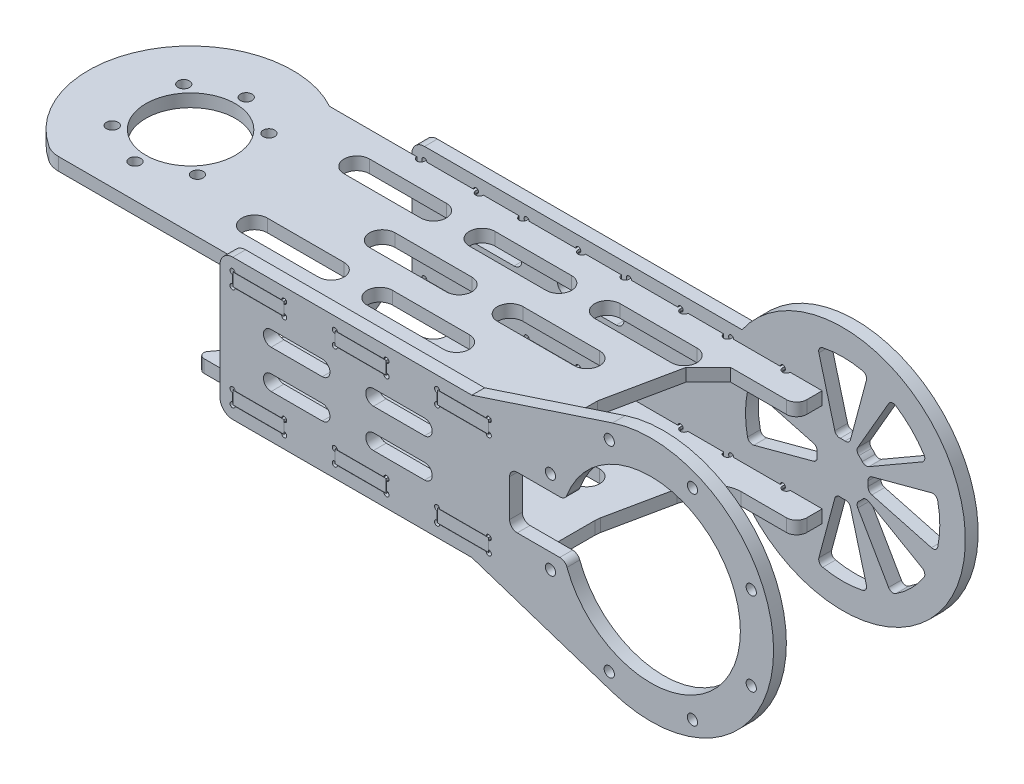
SolidWorks part; units mm, degrees
material "Thornel Mat VMA"
ref_plane "前视基准面" through (0, 0, 0) normal (0, 0, 1) x (1, 0, 0)
ref_plane "上视基准面" through (0, 0, 0) normal (0, 1, 0) x (1, 0, 0)
ref_plane "右视基准面" through (0, 0, 0) normal (1, 0, 0) x (0, 0, -1)
other "Configuration Table"
sketch "草图1" plane through (0, 0, 0) normal (0, 0, 1) x (1, 0, 0)
  line L0 (-270, 0) -> (0, 0)
  dimension "D1" = 270
extrude "拉伸-薄壁1" add sketch "草图1" along normal blind 200 thin
sketch "草图2" plane through (0, 0, 0) normal (0, 1, 0) x (1, 0, 0)
  line L0 (-270, -200) -> (0, -200) construction
  line L4 (-230, -165) -> (-230, -8.8813) construction
  line L5 (-230, -165) -> (-213.3385, -151.0194) construction
  line L6 (-270, -200) -> (-270, 0) construction
  line L7 (-247.5, -165) -> (-212.5, -165) construction
  line L8 (-270, -165) -> (-270, 0)
  line L9 (-270, 0) -> (0, 0) construction
  line L10 (-270, 0) -> (0, 0)
  line L11 (0, -200) -> (0, 0) construction
  line L12 (0, -130) -> (0, 0)
  line L13 (-210.6351, -130) -> (0, -130)
  line L14 (-270, -165) -> (-270, -200)
  line L15 (-270, -200) -> (-249.3649, -200)
  circle A0 centre (-230, -165) radius 21.75 construction
  circle A2 centre (-230, -143.25) radius 2.25
  circle A3 centre (-213.3385, -151.0194) radius 2.25
  circle A4 centre (-246.6615, -151.0194) radius 2.25
  circle A17 centre (-230, -165) radius 17.5
  circle A19 centre (-213.3385, -178.9806) radius 2.25
  circle A20 centre (-230, -186.75) radius 2.25
  circle A21 centre (-246.6615, -178.9806) radius 2.25
  arc A22 (-210.6351, -130) -> (-270, -165) centre (-230, -165) ccw
  arc A24 (-210.6351, -130) -> (-249.3649, -200) centre (-230, -165) ccw
  line M4 (0, 0) -> (-270, 0)
  line M5 (-270, 0) -> (-270, -200)
  line M6 (-270, -200) -> (0, -200)
  line M7 (0, -200) -> (0, 0)
  dimension "D1" = 35
  dimension "D2" = 43.5
  dimension "D4" = 4.5
  dimension "D6" = 80
  dimension "D7" = 35
  dimension "D9" = 35
  dimension "D3" = 40
  dimension "D5" = 50
extrude "切除-拉伸1" cut sketch "草图2" against normal blind 10 contours A22 L13 M7 M4 M5 | A24 M5 M6 | A21 | A17 | A4 | A2 | A3 | A19 | A20
fillet "圆角4" radius 10 1 edges at (-249.3649, -2.5, 200)
sketch "草图5" plane through (0, -5, 0) normal (0, -1, 0) x (1, 0, 0)
  line L0 (-246.5831, 200) -> (0, 200) construction
  line L2 (-180, 200) -> (-20, 200)
  line L3 (-180, 200) -> (-180, 206)
  line L4 (-180, 206) -> (-20, 206)
  line L5 (-20, 200) -> (-20, 206)
  line L6 (0, 200) -> (0, 130) construction
  line L7 (-210.6351, 130) -> (0, 130) construction
  line L8 (-180, 130) -> (-20, 130)
  line L9 (-180, 130) -> (-180, 124)
  line L10 (-180, 124) -> (-20, 124)
  line L11 (-20, 130) -> (-20, 124)
  circle A0 centre (-230, 165) radius 17.5 construction
  dimension "D1" = 6
  dimension "D2" = 50
  dimension "D3" = 20
  dimension "D4" = 6
  dimension "D5" = 20
  dimension "D6" = 50
extrude "凸台-拉伸1" add sketch "草图5" against normal blind 5
sketch "草图6" plane through (0, -5, 0) normal (0, -1, 0) x (1, 0, 0)
  line L0 (-180, 200) -> (-176.5, 200)
  line L1 (-173.5, 200) -> (-173.5, 205)
  line L2 (-173.5, 205) -> (-153.5, 205)
  line L3 (-153.5, 205) -> (-153.5, 200)
  line L4 (-150.5, 200) -> (-136.5, 200)
  line L5 (-180, 206) -> (-180, 200) construction
  line L6 (-20, 206) -> (-180, 206) construction
  line L7 (-20, 206) -> (-180, 206)
  line L8 (-180, 206) -> (-180, 200)
  line L9 (-133.5, 200) -> (-133.5, 205)
  line L10 (-133.5, 205) -> (-113.5, 205)
  line L11 (-113.5, 205) -> (-113.5, 200)
  line L12 (-110.5, 200) -> (-96.5, 200)
  line L13 (-93.5, 200) -> (-93.5, 205)
  line L14 (-93.5, 205) -> (-73.5, 205)
  line L15 (-73.5, 205) -> (-73.5, 200)
  line L16 (-70.5, 200) -> (-56.5, 200)
  line L17 (-53.5, 200) -> (-53.5, 205)
  line L18 (-53.5, 205) -> (-33.5, 205)
  line L19 (-33.5, 205) -> (-33.5, 200)
  line L20 (-30.5, 200) -> (-20, 200)
  line L21 (-20, 206) -> (-20, 200)
  line L22 (-212.5, 165) -> (-121.566, 165) construction
  line L23 (-20, 124) -> (-20, 130)
  line L24 (-30.5, 130) -> (-20, 130)
  line L25 (-33.5, 125) -> (-33.5, 130)
  line L26 (-53.5, 125) -> (-33.5, 125)
  line L27 (-53.5, 130) -> (-53.5, 125)
  line L28 (-70.5, 130) -> (-56.5, 130)
  line L29 (-73.5, 125) -> (-73.5, 130)
  line L30 (-93.5, 125) -> (-73.5, 125)
  line L31 (-93.5, 130) -> (-93.5, 125)
  line L32 (-110.5, 130) -> (-96.5, 130)
  line L33 (-113.5, 125) -> (-113.5, 130)
  line L34 (-133.5, 125) -> (-113.5, 125)
  line L35 (-133.5, 130) -> (-133.5, 125)
  line L36 (-180, 124) -> (-180, 130)
  line L37 (-20, 124) -> (-180, 124)
  line L38 (-150.5, 130) -> (-136.5, 130)
  line L39 (-153.5, 125) -> (-153.5, 130)
  line L40 (-173.5, 125) -> (-153.5, 125)
  line L41 (-173.5, 130) -> (-173.5, 125)
  line L42 (-180, 130) -> (-176.5, 130)
  arc A1 (-176.5, 200) -> (-173.5, 200) centre (-175, 200) ccw
  arc A2 (-153.5, 200) -> (-150.5, 200) centre (-152, 200) ccw
  arc A3 (-136.5, 200) -> (-133.5, 200) centre (-135, 200) ccw
  arc A4 (-113.5, 200) -> (-110.5, 200) centre (-112, 200) ccw
  arc A5 (-96.5, 200) -> (-93.5, 200) centre (-95, 200) ccw
  arc A6 (-73.5, 200) -> (-70.5, 200) centre (-72, 200) ccw
  arc A7 (-56.5, 200) -> (-53.5, 200) centre (-55, 200) ccw
  arc A8 (-33.5, 200) -> (-30.5, 200) centre (-32, 200) ccw
  circle A9 centre (-230, 165) radius 17.5 construction
  arc A10 (-33.5, 130) -> (-30.5, 130) centre (-32, 130) cw
  arc A11 (-56.5, 130) -> (-53.5, 130) centre (-55, 130) cw
  arc A12 (-73.5, 130) -> (-70.5, 130) centre (-72, 130) cw
  arc A13 (-96.5, 130) -> (-93.5, 130) centre (-95, 130) cw
  arc A14 (-113.5, 130) -> (-110.5, 130) centre (-112, 130) cw
  arc A15 (-136.5, 130) -> (-133.5, 130) centre (-135, 130) cw
  arc A16 (-153.5, 130) -> (-150.5, 130) centre (-152, 130) cw
  arc A17 (-176.5, 130) -> (-173.5, 130) centre (-175, 130) cw
  dimension "D1" = 3
  dimension "D2" = 5
  dimension "D5" = 3
  dimension "D8" = 6
  dimension "D3" = 1
  dimension "D4" = 20
  dimension "D6" = 14
  dimension "D7" = 6
  dimension "D10" = 20
  dimension "D9" = 20
extrude "切除-拉伸2" cut sketch "草图6" against normal blind 5
sketch "草图7" plane through (0, -5, 0) normal (0, -1, 0) x (1, 0, 0)
  line L0 (-185, 185) -> (-155, 185) construction
  line L1 (-185, 190) -> (-155, 190)
  line L2 (-185, 180) -> (-155, 180)
  line L3 (-246.5831, 200) -> (-176.5, 200) construction
  line L4 (-136, 185) -> (-106, 185) construction
  line L5 (-136, 190) -> (-106, 190)
  line L6 (-136, 180) -> (-106, 180)
  line L7 (-87, 185) -> (-57, 185) construction
  line L8 (-87, 190) -> (-57, 190) construction
  line L9 (-87, 180) -> (-57, 180) construction
  line L10 (-185, 165) -> (-155, 165) construction
  line L11 (-185, 170) -> (-155, 170) construction
  line L12 (-185, 160) -> (-155, 160) construction
  line L13 (-155, 165) -> (-125, 165) construction
  line L14 (-155, 170) -> (-125, 170)
  line L15 (-155, 160) -> (-125, 160)
  line L16 (-105, 165) -> (-75, 165) construction
  line L17 (-105, 170) -> (-75, 170)
  line L18 (-105, 160) -> (-75, 160)
  line L19 (-125, 165) -> (-105, 165) construction
  line L20 (-87, 145) -> (-57, 145) construction
  line L21 (-87, 140) -> (-57, 140)
  line L22 (-87, 150) -> (-57, 150)
  line L23 (-136, 145) -> (-106, 145) construction
  line L24 (-136, 140) -> (-106, 140)
  line L25 (-136, 150) -> (-106, 150)
  line L26 (-185, 145) -> (-155, 145) construction
  line L27 (-185, 140) -> (-155, 140)
  line L28 (-185, 150) -> (-155, 150)
  arc A0 (-185, 190) -> (-185, 180) centre (-185, 185) ccw
  arc A1 (-155, 180) -> (-155, 190) centre (-155, 185) ccw
  circle A2 centre (-230, 165) radius 17.5 construction
  arc A3 (-136, 190) -> (-136, 180) centre (-136, 185) ccw
  arc A4 (-106, 180) -> (-106, 190) centre (-106, 185) ccw
  arc A5 (-87, 190) -> (-87, 180) centre (-87, 185) ccw construction
  arc A6 (-57, 180) -> (-57, 190) centre (-57, 185) ccw construction
  arc A7 (-185, 170) -> (-185, 160) centre (-185, 165) ccw construction
  arc A8 (-155, 160) -> (-155, 170) centre (-155, 165) ccw construction
  arc A9 (-155, 170) -> (-155, 160) centre (-155, 165) ccw
  arc A10 (-125, 160) -> (-125, 170) centre (-125, 165) ccw
  arc A11 (-105, 170) -> (-105, 160) centre (-105, 165) ccw
  arc A12 (-75, 160) -> (-75, 170) centre (-75, 165) ccw
  arc A13 (-87, 140) -> (-87, 150) centre (-87, 145) cw
  arc A14 (-57, 150) -> (-57, 140) centre (-57, 145) cw
  arc A15 (-136, 140) -> (-136, 150) centre (-136, 145) cw
  arc A16 (-106, 150) -> (-106, 140) centre (-106, 145) cw
  arc A17 (-185, 140) -> (-185, 150) centre (-185, 145) cw
  arc A18 (-155, 150) -> (-155, 140) centre (-155, 145) cw
  point P2 (-170, 185)
  point P14 (-121, 185)
  point P21 (-72, 185)
  point P28 (-170, 165)
  point P35 (-140, 165)
  point P42 (-90, 165)
  point P50 (-72, 145)
  point P57 (-121, 145)
  point P64 (-170, 145)
  dimension "D1" = 30
  dimension "D2" = 10
  dimension "D3" = 15
  dimension "D4" = 60
  dimension "D6" = 34
  dimension "D8" = 35
  dimension "D10" = 30
  dimension "D12" = 50
  dimension "D5" = 3
  dimension "D7" = 2
  dimension "D9" = 2
  dimension "D11" = 2
extrude "切除-拉伸3" cut sketch "草图7" against normal blind 5
pattern_linear "阵列(线性)1" count 2 spacing 40 along (0, 1, 0) of bodies 111
sketch "草图8" plane through (0, 0, 205) normal (0, 0, 1) x (1, 0, 0)
  line L0 (-173.5, -5) -> (-153.5, -5) construction
  line L1 (-178.5, 45) -> (-49.3415, 45)
  line L2 (-178.5, 45) -> (-178.5, -10)
  line L3 (-178.5, -10) -> (-49.3415, -10)
  line L5 (-153.5, 0) -> (-153.5, -5) construction
  line L6 (-173.5, 0) -> (-153.5, 0) construction
  line L7 (-173.5, 0) -> (-173.5, -5) construction
  line L8 (-173.5, -5) -> (-153.5, -5) construction
  line L9 (-153.5, 0) -> (-153.5, -5) construction
  line L10 (-173.5, 0) -> (-153.5, 0) construction
  line L11 (-173.5, 0) -> (-173.5, -5) construction
  line L12 (-173.6, -0.9) -> (-173.6, -4.1)
  line L13 (-172.6, -5.1) -> (-154.4, -5.1)
  line L14 (-153.4, -0.9) -> (-153.4, -4.1)
  line L15 (-172.6, 0.1) -> (-154.4, 0.1)
  line L16 (-173.5, 40) -> (-153.5, 40) construction
  line L17 (-270, 40) -> (-270, 35) construction
  line L18 (-173.6, 0.1) -> (-173.6, -5.1) construction
  line L19 (-173.6, 0.1) -> (-153.4, 0.1) construction
  line L20 (-173.6, -5.1) -> (-153.4, -5.1) construction
  line L21 (-153.4, 0.1) -> (-153.4, -5.1) construction
  line L22 (-133.6, -0.9) -> (-133.6, -4.1)
  line L23 (-132.6, -5.1) -> (-114.4, -5.1)
  line L24 (-113.4, -0.9) -> (-113.4, -4.1)
  line L25 (-132.6, 0.1) -> (-114.4, 0.1)
  line L26 (-133.5, -5) -> (-113.5, -5) construction
  line L27 (-113.5, 0) -> (-113.5, -5) construction
  line L28 (-133.5, 0) -> (-113.5, 0) construction
  line L29 (-133.5, 0) -> (-133.5, -5) construction
  line L30 (-93.6, -0.9) -> (-93.6, -4.1)
  line L31 (-92.6, -5.1) -> (-74.4, -5.1)
  line L32 (-73.4, -0.9) -> (-73.4, -4.1)
  line L33 (-92.6, 0.1) -> (-74.4, 0.1)
  line L34 (-93.5, -5) -> (-73.5, -5) construction
  line L35 (-73.5, 0) -> (-73.5, -5) construction
  line L36 (-93.5, 0) -> (-73.5, 0) construction
  line L37 (-93.5, 0) -> (-93.5, -5) construction
  line L38 (-53.6, -0.9) -> (-53.6, -4.1)
  line L39 (-52.6, -5.1) -> (-34.4, -5.1)
  line L40 (-33.4, -0.9) -> (-33.4, -4.1)
  line L41 (-52.6, 0.1) -> (-34.4, 0.1)
  line L42 (-53.5, -5) -> (-33.5, -5) construction
  line L43 (-33.5, 0) -> (-33.5, -5) construction
  line L44 (-53.5, 0) -> (-33.5, 0) construction
  line L45 (-53.5, 0) -> (-53.5, -5) construction
  line L46 (-133.6, 39.1) -> (-133.6, 35.9)
  line L47 (-132.6, 34.9) -> (-114.4, 34.9)
  line L48 (-113.4, 39.1) -> (-113.4, 35.9)
  line L49 (-132.6, 40.1) -> (-114.4, 40.1)
  line L50 (-133.5, 35) -> (-113.5, 35) construction
  line L51 (-113.5, 40) -> (-113.5, 35) construction
  line L52 (-133.5, 40) -> (-113.5, 40) construction
  line L53 (-133.5, 40) -> (-133.5, 35) construction
  line L54 (-93.6, 39.1) -> (-93.6, 35.9)
  line L55 (-92.6, 34.9) -> (-74.4, 34.9)
  line L56 (-73.4, 39.1) -> (-73.4, 35.9)
  line L57 (-92.6, 40.1) -> (-74.4, 40.1)
  line L58 (-93.5, 35) -> (-73.5, 35) construction
  line L59 (-73.5, 40) -> (-73.5, 35) construction
  line L60 (-93.5, 40) -> (-73.5, 40) construction
  line L61 (-93.5, 40) -> (-93.5, 35) construction
  line L62 (-53.6, 39.1) -> (-53.6, 35.9)
  line L63 (-52.6, 34.9) -> (-34.4, 34.9)
  line L64 (-33.4, 39.1) -> (-33.4, 35.9)
  line L65 (-52.6, 40.1) -> (-34.4, 40.1)
  line L66 (-53.5, 35) -> (-33.5, 35) construction
  line L67 (-33.5, 40) -> (-33.5, 35) construction
  line L68 (-53.5, 40) -> (-33.5, 40) construction
  line L69 (-53.5, 40) -> (-53.5, 35) construction
  line L70 (-173.6, 39.1) -> (-173.6, 35.9)
  line L71 (-172.6, 34.9) -> (-154.4, 34.9)
  line L72 (-153.4, 39.1) -> (-153.4, 35.9)
  line L73 (-172.6, 40.1) -> (-154.4, 40.1)
  line L74 (-173.5, 35) -> (-153.5, 35) construction
  line L75 (-153.5, 40) -> (-153.5, 35) construction
  line L76 (-173.5, 40) -> (-153.5, 40) construction
  line L77 (-173.5, 40) -> (-173.5, 35) construction
  arc A0 (-172.6, 0.1) -> (-173.6, -0.9) centre (-173.6, 0.1) ccw
  arc A1 (-173.6, -4.1) -> (-172.6, -5.1) centre (-173.6, -5.1) ccw
  arc A2 (-153.4, -0.9) -> (-154.4, 0.1) centre (-153.4, 0.1) ccw
  arc A3 (-154.4, -5.1) -> (-153.4, -4.1) centre (-153.4, -5.1) ccw
  arc A5 (-132.6, 0.1) -> (-133.6, -0.9) centre (-133.6, 0.1) ccw
  arc A6 (-133.6, -4.1) -> (-132.6, -5.1) centre (-133.6, -5.1) ccw
  arc A7 (-113.4, -0.9) -> (-114.4, 0.1) centre (-113.4, 0.1) ccw
  arc A8 (-114.4, -5.1) -> (-113.4, -4.1) centre (-113.4, -5.1) ccw
  arc A9 (-92.6, 0.1) -> (-93.6, -0.9) centre (-93.6, 0.1) ccw
  arc A10 (-93.6, -4.1) -> (-92.6, -5.1) centre (-93.6, -5.1) ccw
  arc A11 (-73.4, -0.9) -> (-74.4, 0.1) centre (-73.4, 0.1) ccw
  arc A12 (-74.4, -5.1) -> (-73.4, -4.1) centre (-73.4, -5.1) ccw
  arc A13 (-52.6, 0.1) -> (-53.6, -0.9) centre (-53.6, 0.1) ccw
  arc A14 (-53.6, -4.1) -> (-52.6, -5.1) centre (-53.6, -5.1) ccw
  arc A15 (-33.4, -0.9) -> (-34.4, 0.1) centre (-33.4, 0.1) ccw
  arc A16 (-34.4, -5.1) -> (-33.4, -4.1) centre (-33.4, -5.1) ccw
  arc A17 (-132.6, 40.1) -> (-133.6, 39.1) centre (-133.6, 40.1) ccw
  arc A18 (-133.6, 35.9) -> (-132.6, 34.9) centre (-133.6, 34.9) ccw
  arc A19 (-113.4, 39.1) -> (-114.4, 40.1) centre (-113.4, 40.1) ccw
  arc A20 (-114.4, 34.9) -> (-113.4, 35.9) centre (-113.4, 34.9) ccw
  arc A21 (-92.6, 40.1) -> (-93.6, 39.1) centre (-93.6, 40.1) ccw
  arc A22 (-93.6, 35.9) -> (-92.6, 34.9) centre (-93.6, 34.9) ccw
  arc A23 (-73.4, 39.1) -> (-74.4, 40.1) centre (-73.4, 40.1) ccw
  arc A24 (-74.4, 34.9) -> (-73.4, 35.9) centre (-73.4, 34.9) ccw
  arc A25 (-52.6, 40.1) -> (-53.6, 39.1) centre (-53.6, 40.1) ccw
  arc A26 (-53.6, 35.9) -> (-52.6, 34.9) centre (-53.6, 34.9) ccw
  arc A27 (-33.4, 39.1) -> (-34.4, 40.1) centre (-33.4, 40.1) ccw
  arc A28 (-34.4, 34.9) -> (-33.4, 35.9) centre (-33.4, 34.9) ccw
  arc A29 (-172.6, 40.1) -> (-173.6, 39.1) centre (-173.6, 40.1) ccw
  arc A30 (-173.6, 35.9) -> (-172.6, 34.9) centre (-173.6, 34.9) ccw
  arc A31 (-153.4, 39.1) -> (-154.4, 40.1) centre (-153.4, 40.1) ccw
  arc A32 (-154.4, 34.9) -> (-153.4, 35.9) centre (-153.4, 34.9) ccw
  arc A33 (-49.3415, -10) -> (-49.3415, 45) centre (-10, 17.5) ccw
  point P16 (-163.5, 0.1)
  dimension "D2" = 2
  dimension "D3" = 2
  dimension "D4" = 2
  dimension "D5" = 2
  dimension "D15" = 48
  dimension "D6" = 15
  dimension "D7" = 5
  dimension "D8" = 5
  dimension "D9" = 260
  dimension "D12" = 34.8
  dimension "D13" = 19.8
  dimension "D14" = 19.8
  dimension "D16" = 27.5
  dimension "D1" = 0.1
  dimension "D10" = 4
  dimension "D11" = 2
extrude "凸台-拉伸2" add sketch "草图8" against normal blind 5 separate body
fillet "圆角5" radius 5 2 edges at (-178.5, -10, 202.5) (-178.5, 45, 202.5)
sketch "草图9" plane through (0, 40, 0) normal (0, 1, 0) x (1, 0, 0)
  line L3 (-58.5, -217.9377) -> (0, -217.9377)
  line L7 (-58.5, -217.9377) -> (-58.5, -177.3247)
  line L12 (-43.842, -140) -> (0, -140)
  line L13 (0, -140) -> (0, -217.9377)
  line L14 (0, -200) -> (0, -130) construction
  line L15 (38, -200) -> (-49.3415, -200) construction
  line L17 (-73.5, -205) -> (-73.5, -200) construction
  line L18 (-43.842, -140) -> (-52.5419, -148.6999)
  line L19 (-52.5419, -148.6999) -> (-58.5, -177.3247)
  dimension "D1" = 15
  dimension "D3" = 60
extrude "切除-拉伸4" cut sketch "草图9" against normal through all
fillet "圆角6" radius 10 3 edges at (-43.842, -2.5, 140) (-52.5419, -2.5, 148.6999) (-58.5, -2.5, 177.3247)
pattern_linear "阵列(线性)2" count 2 spacing 75 along (0, 0, -1) of bodies 113
fillet "圆角9" radius 4 1 edges at (0, -2.5, 140)
fillet "圆角10" radius 4 1 edges at (0, 37.5, 140)
sketch "草图10" plane through (0, 0, 200) normal (0, 0, -1) x (-1, 0, 0)
  line L1 (28.3121, 42.8923) -> (56.7425, 42.8923)
  line L2 (28.3121, 42.8923) -> (28.3121, 32.3207)
  line L3 (28.3121, 32.3207) -> (56.7425, 32.3207)
  line L4 (56.7425, 42.8923) -> (56.7425, 32.3207)
  line L5 (28.3121, 3.4798) -> (56.7425, 3.4798)
  line L6 (28.3121, 3.4798) -> (28.3121, -7.5024)
  line L7 (28.3121, -7.5024) -> (56.7425, -7.5024)
  line L8 (56.7425, 3.4798) -> (56.7425, -7.5024)
extrude "凸台-拉伸3" add sketch "草图10" against normal blind 5
sketch "草图11" plane through (0, 0, 205) normal (0, 0, 1) x (1, 0, 0)
  line L0 (-10, 17.5) -> (14.3098, 17.5) construction
  line L1 (-10, 17.5) -> (-49.2649, 33.764) construction
  line L2 (-62.2649, 27.764) -> (-45.6099, 27.764)
  line L3 (-65.2649, 24.764) -> (-65.2649, 10.236)
  line L4 (-62.2649, 7.236) -> (-45.6099, 7.236)
  circle A0 centre (-10, 17.5) radius 42.5 construction
  circle A1 centre (6.264, 56.7649) radius 2
  circle A2 centre (29.2649, 33.764) radius 2
  circle A3 centre (29.2649, 1.236) radius 2
  circle A4 centre (6.264, -21.7649) radius 2
  circle A5 centre (-26.264, -21.7649) radius 2
  circle A6 centre (-49.2649, 1.236) radius 2
  circle A7 centre (-49.2649, 33.764) radius 2
  circle A8 centre (-26.264, 56.7649) radius 2
  arc A9 (-42.7986, 5.2831) -> (-42.7986, 29.7169) centre (-10, 17.5) ccw
  arc A10 (-62.2649, 27.764) -> (-65.2649, 24.764) centre (-62.2649, 24.764) ccw
  arc A11 (-65.2649, 10.236) -> (-62.2649, 7.236) centre (-62.2649, 10.236) ccw
  arc A12 (-45.6099, 7.236) -> (-42.7986, 5.2831) centre (-45.6099, 4.236) cw
  arc A13 (-45.6099, 27.764) -> (-42.7986, 29.7169) centre (-45.6099, 30.764) ccw
  point P22 (-10, 17.5)
  dimension "D1" = 85
  dimension "D2" = 4
  dimension "D4" = 157.5
  dimension "D7" = 70
  dimension "D9" = 3
  dimension "D5" = 6
  dimension "D6" = 6
  dimension "D8" = 16
  dimension "D3" = 8
extrude "切除-拉伸5" cut sketch "草图11" against normal blind 10
sketch "草图12" plane through (0, 0, 205) normal (0, 0, 1) x (1, 0, 0)
  line L0 (-80, 45) -> (-25.0018, 63.0955)
  line L1 (-49.3415, 45) -> (-173.5, 45) construction
  line L2 (-49.3415, 45) -> (-80, 45)
  line L3 (-10, 17.5) -> (11.5548, 17.5) construction
  line L4 (-80, -10) -> (-25.0018, -28.0955)
  line L5 (-80, -10) -> (-49.3415, -10)
  arc A0 (-49.3415, -10) -> (-49.3415, 45) centre (-10, 17.5) ccw construction
  arc A1 (-25.0018, 63.0955) -> (-49.3415, 45) centre (-10, 17.5) ccw
  arc A2 (-25.0018, -28.0955) -> (-49.3415, -10) centre (-10, 17.5) cw
  dimension "D1" = 70
extrude "凸台-拉伸4" add sketch "草图12" against normal blind 5
sketch "草图13" plane through (0, 0, 125) normal (0, 0, -1) x (-1, 0, 0)
  line L0 (10, 17.5) -> (-28, 17.5) construction
  line L1 (-21.1288, 35.4722) -> (-0.247, 23.4161)
  line L2 (4.0839, 27.747) -> (-7.9722, 48.6288)
  line L3 (0.6969, 52.2196) -> (6.9376, 28.929)
  line L4 (13.0624, 28.929) -> (19.3031, 52.2196)
  line L5 (27.9722, 48.6288) -> (15.9161, 27.747) construction
  line L6 (20.247, 23.4161) -> (41.1288, 35.4722) construction
  line L7 (44.7196, 26.8031) -> (21.429, 20.5624)
  line L8 (21.429, 14.4376) -> (44.7196, 8.1969)
  line L9 (41.1288, -0.4722) -> (20.247, 11.5839) construction
  line L10 (15.9161, 7.253) -> (27.9722, -13.6288) construction
  line L11 (19.3031, -17.2196) -> (13.0624, 6.071)
  line L12 (6.9376, 6.071) -> (0.6969, -17.2196)
  line L13 (-7.9722, -13.6288) -> (4.0839, 7.253)
  line L14 (-0.247, 11.5839) -> (-21.1288, -0.4722)
  line L15 (-24.7196, 8.1969) -> (-1.429, 14.4376)
  line L16 (-1.429, 20.5624) -> (-24.7196, 26.8031)
  arc A0 (-10.7989, 49.3026) -> (-21.8026, 38.2989) centre (10, 17.5) ccw
  arc A1 (3.6266, 25.2058) -> (2.2942, 23.8734) centre (10, 17.5) ccw
  arc A2 (4.0839, 27.747) -> (3.6266, 25.2058) centre (2.3519, 26.747) cw
  arc A3 (-0.247, 23.4161) -> (2.2942, 23.8734) centre (0.753, 25.1481) ccw
  arc A4 (-7.9722, 48.6288) -> (-10.7989, 49.3026) centre (-9.7043, 47.6288) ccw
  arc A5 (-21.1288, 35.4722) -> (-21.8026, 38.2989) centre (-20.1288, 37.2043) cw
  arc A6 (17.7808, 54.6949) -> (2.2192, 54.6949) centre (10, 17.5) ccw
  arc A7 (10.9421, 27.4555) -> (9.0579, 27.4555) centre (10, 17.5) ccw
  arc A8 (13.0624, 28.929) -> (10.9421, 27.4555) centre (11.1305, 29.4466) cw
  arc A9 (6.9376, 28.929) -> (9.0579, 27.4555) centre (8.8695, 29.4466) ccw
  arc A10 (19.3031, 52.2196) -> (17.7808, 54.6949) centre (17.3712, 52.7373) ccw
  arc A11 (0.6969, 52.2196) -> (2.2192, 54.6949) centre (2.6288, 52.7373) cw
  arc A12 (41.8026, 38.2989) -> (30.7989, 49.3026) centre (10, 17.5) ccw construction
  arc A13 (17.7058, 23.8734) -> (16.3734, 25.2058) centre (10, 17.5) ccw construction
  arc A14 (20.247, 23.4161) -> (17.7058, 23.8734) centre (19.247, 25.1481) cw construction
  arc A15 (15.9161, 27.747) -> (16.3734, 25.2058) centre (17.6481, 26.747) ccw construction
  arc A16 (41.1288, 35.4722) -> (41.8026, 38.2989) centre (40.1288, 37.2043) ccw construction
  arc A17 (27.9722, 48.6288) -> (30.7989, 49.3026) centre (29.7043, 47.6288) cw construction
  arc A18 (47.1949, 9.7192) -> (47.1949, 25.2808) centre (10, 17.5) ccw
  arc A19 (19.9555, 16.5579) -> (19.9555, 18.4421) centre (10, 17.5) ccw
  arc A20 (21.429, 14.4376) -> (19.9555, 16.5579) centre (21.9466, 16.3695) cw
  arc A21 (21.429, 20.5624) -> (19.9555, 18.4421) centre (21.9466, 18.6305) ccw
  arc A22 (44.7196, 8.1969) -> (47.1949, 9.7192) centre (45.2373, 10.1288) ccw
  arc A23 (44.7196, 26.8031) -> (47.1949, 25.2808) centre (45.2373, 24.8712) cw
  arc A24 (30.7989, -14.3026) -> (41.8026, -3.2989) centre (10, 17.5) ccw construction
  arc A25 (16.3734, 9.7942) -> (17.7058, 11.1266) centre (10, 17.5) ccw construction
  arc A26 (15.9161, 7.253) -> (16.3734, 9.7942) centre (17.6481, 8.253) cw construction
  arc A27 (20.247, 11.5839) -> (17.7058, 11.1266) centre (19.247, 9.8519) ccw construction
  arc A28 (27.9722, -13.6288) -> (30.7989, -14.3026) centre (29.7043, -12.6288) ccw construction
  arc A29 (41.1288, -0.4722) -> (41.8026, -3.2989) centre (40.1288, -2.2043) cw construction
  arc A30 (2.2192, -19.6949) -> (17.7808, -19.6949) centre (10, 17.5) ccw
  arc A31 (9.0579, 7.5445) -> (10.9421, 7.5445) centre (10, 17.5) ccw
  arc A32 (6.9376, 6.071) -> (9.0579, 7.5445) centre (8.8695, 5.5534) cw
  arc A33 (13.0624, 6.071) -> (10.9421, 7.5445) centre (11.1305, 5.5534) ccw
  arc A34 (0.6969, -17.2196) -> (2.2192, -19.6949) centre (2.6288, -17.7373) ccw
  arc A35 (19.3031, -17.2196) -> (17.7808, -19.6949) centre (17.3712, -17.7373) cw
  arc A36 (-21.8026, -3.2989) -> (-10.7989, -14.3026) centre (10, 17.5) ccw
  arc A37 (2.2942, 11.1266) -> (3.6266, 9.7942) centre (10, 17.5) ccw
  arc A38 (-0.247, 11.5839) -> (2.2942, 11.1266) centre (0.753, 9.8519) cw
  arc A39 (4.0839, 7.253) -> (3.6266, 9.7942) centre (2.3519, 8.253) ccw
  arc A40 (-21.1288, -0.4722) -> (-21.8026, -3.2989) centre (-20.1288, -2.2043) ccw
  arc A41 (-7.9722, -13.6288) -> (-10.7989, -14.3026) centre (-9.7043, -12.6288) cw
  arc A42 (-27.1949, 25.2808) -> (-27.1949, 9.7192) centre (10, 17.5) ccw
  arc A43 (0.0445, 18.4421) -> (0.0445, 16.5579) centre (10, 17.5) ccw
  arc A44 (-1.429, 20.5624) -> (0.0445, 18.4421) centre (-1.9466, 18.6305) cw
  arc A45 (-1.429, 14.4376) -> (0.0445, 16.5579) centre (-1.9466, 16.3695) ccw
  arc A46 (-24.7196, 26.8031) -> (-27.1949, 25.2808) centre (-25.2373, 24.8712) ccw
  arc A47 (-24.7196, 8.1969) -> (-27.1949, 9.7192) centre (-25.2373, 10.1288) cw
  point P108 (10, 17.5)
  dimension "D1" = 20
  dimension "D2" = 76
  dimension "D5" = 2
  dimension "D3" = 30
  dimension "D4" = 30
  dimension "D6" = 8
extrude "切除-拉伸6" cut sketch "草图13" against normal blind 5
sketch "草图14" plane through (0, 40, 0) normal (0, 1, 0) x (1, 0, 0)
  line L0 (-30.5, -130) -> (0, -130) construction
  line L1 (-18, -130) -> (12.2993, -130)
  line L2 (-18, -130) -> (-18, -140.5182)
  line L3 (-18, -140.5182) -> (12.2993, -140.5182)
  line L4 (12.2993, -130) -> (12.2993, -140.5182)
  line L5 (0, -136) -> (0, -130) construction
  dimension "D1" = 18
extrude "切除-拉伸7" cut sketch "草图14" against normal through all
fillet "圆角11" radius 4 2 edges at (-18, 37.5, 140) (-18, -2.5, 140)
sketch "草图15" plane through (0, 0, 125) normal (0, 0, -1) x (-1, 0, 0)
  line L0 (58.5, 25) -> (78.5, 25) construction
  line L1 (58.5, 28) -> (78.5, 28) construction
  line L2 (58.5, 22) -> (78.5, 22) construction
  line L3 (49.3415, 45) -> (173.5, 45) construction
  line L4 (178.5, 40) -> (178.5, -5) construction
  line L5 (98.5, 25) -> (118.5, 25) construction
  line L6 (98.5, 28) -> (118.5, 28)
  line L7 (98.5, 22) -> (118.5, 22)
  line L8 (138.5, 25) -> (158.5, 25) construction
  line L9 (138.5, 28) -> (158.5, 28)
  line L10 (138.5, 22) -> (158.5, 22)
  line L11 (98.5, 10) -> (118.5, 10) construction
  line L12 (98.5, 13) -> (118.5, 13)
  line L13 (98.5, 7) -> (118.5, 7)
  line L14 (138.5, 10) -> (158.5, 10) construction
  line L15 (138.5, 13) -> (158.5, 13)
  line L16 (138.5, 7) -> (158.5, 7)
  line L17 (58.5, 10) -> (78.5, 10) construction
  line L18 (58.5, 13) -> (78.5, 13) construction
  line L19 (58.5, 7) -> (78.5, 7) construction
  line L20 (173.5, -10) -> (49.3415, -10) construction
  arc A0 (58.5, 28) -> (58.5, 22) centre (58.5, 25) ccw construction
  arc A1 (78.5, 22) -> (78.5, 28) centre (78.5, 25) ccw construction
  arc A2 (98.5, 28) -> (98.5, 22) centre (98.5, 25) ccw
  arc A3 (118.5, 22) -> (118.5, 28) centre (118.5, 25) ccw
  arc A4 (138.5, 28) -> (138.5, 22) centre (138.5, 25) ccw
  arc A5 (158.5, 22) -> (158.5, 28) centre (158.5, 25) ccw
  arc A6 (98.5, 13) -> (98.5, 7) centre (98.5, 10) ccw
  arc A7 (118.5, 7) -> (118.5, 13) centre (118.5, 10) ccw
  arc A8 (138.5, 13) -> (138.5, 7) centre (138.5, 10) ccw
  arc A9 (158.5, 7) -> (158.5, 13) centre (158.5, 10) ccw
  arc A10 (58.5, 13) -> (58.5, 7) centre (58.5, 10) ccw construction
  arc A11 (78.5, 7) -> (78.5, 13) centre (78.5, 10) ccw construction
  point P2 (68.5, 25)
  point P15 (108.5, 25)
  point P22 (148.5, 25)
  point P29 (108.5, 10)
  point P36 (148.5, 10)
  point P43 (68.5, 10)
  dimension "D1" = 6
  dimension "D2" = 20
  dimension "D3" = 110
  dimension "D4" = 20
  dimension "D7" = 20
  dimension "D8" = 30
  dimension "D5" = 3
  dimension "D6" = 2
extrude "切除-拉伸8" cut sketch "草图15" against normal through all
sketch "草图16" plane through (0, 0, 0) normal (0, 1, 0) x (1, 0, 0)
  circle A0 centre (-230, -165) radius 50
  dimension "D1" = 100
extrude "切除-拉伸9" cut sketch "草图16" against normal blind 5
sketch "草图17" plane through (0, 0, 0) normal (0, 1, 0) x (1, 0, 0)
  line L0 (-194.2929, -130) -> (-186.285, -130)
  line L1 (-194.2929, -130) -> (-176.5, -130) construction
  line L2 (-194.2929, -200) -> (-186.285, -200)
  line L3 (-246.5831, -200) -> (-178.5, -200) construction
  arc A0 (-186.285, -200) -> (-186.285, -130) centre (-230, -165) ccw
  arc A1 (-194.2929, -200) -> (-194.2929, -130) centre (-230, -165) ccw
  dimension "D1" = 56
extrude "凸台-拉伸5" add sketch "草图17" against normal blind 5
fillet "圆角12" radius 2 2 edges at (-194.2929, -2.5, 200) (-194.2929, -2.5, 130)
